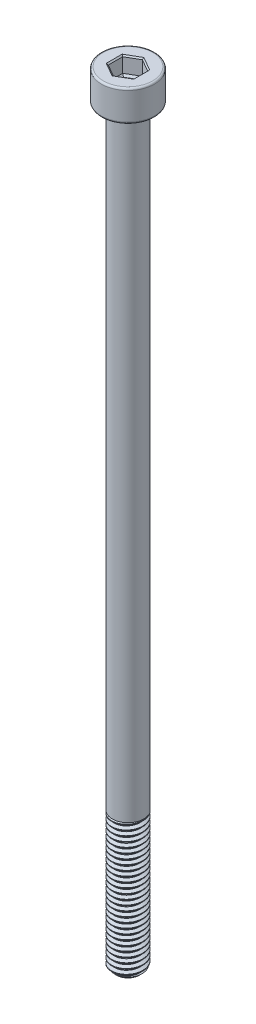
SolidWorks part; units mm, degrees
material "AISI Type A2 Tool Steel"
ref_plane "Front Plane" through (0, 0, 0) normal (0, 0, 1) x (1, 0, 0)
ref_plane "Top Plane" through (0, 0, 0) normal (0, 1, 0) x (1, 0, 0)
ref_plane "Right Plane" through (0, 0, 0) normal (1, 0, 0) x (0, 0, -1)
sketch "Sketch1" plane through (0, 0, 0) normal (0, 1, 0) x (1, 0, 0)
  circle A0 centre (0, 0) radius 2.5
  dimension "D1" = 5
extrude "Boss-Extrude1" add sketch "Sketch1" along normal blind 22
thread "Thread1" pitch 0.8 method cut profile "Thread Profile1" start angle 0, offset 1, length 0, pitch 0.8, diameter 5
ref_plane "Plane1" through (-2.5, 23, 0) normal (0, 0, 1) x (-1, 0, 0)
sketch "Thread Profile1" plane through (-2.5, 23, 0) normal (0, 0, 1) x (-1, 0, 0)
  line L0 (0, 0) -> (0, 0.8) construction
  line L11 (0, 0) -> (0, 0.7)
  line L12 (0, 0.7) -> (-0.433, 0.45)
  line L13 (-0.433, 0.45) -> (-0.433, 0.25)
  line L15 (-0.433, 0.25) -> (0, 0)
  line L17 (-0.433, 0.35) -> (0, 0.35) construction
  point P2 (0, 0)
  dimension "Pitch" = 0.8
  dimension "Profile_Angle" = 60
  dimension "Profile_Land" = 0.2
  dimension "Profile_Height" = 0.433
sketch "Sketch2" plane through (0, 22, 0) normal (0, 1, 0) x (1, 0, 0)
  circle A0 centre (0, 0) radius 2.5
  dimension "D1" = 5
extrude "Boss-Extrude2" add sketch "Sketch2" along normal blind 98
sketch "Sketch3" plane through (0, 120, 0) normal (0, 1, 0) x (1, 0, 0)
  circle A0 centre (0, 0) radius 4.25
  dimension "D1" = 8.5
extrude "Boss-Extrude3" add sketch "Sketch3" along normal blind 5
fillet "Fillet1" radius 0.3 2 edges at (0, 120, 4.25) (0, 125, 4.25)
sketch "Sketch4" plane through (0, 0, 0) normal (0, 0, 1) x (1, 0, 0)
  line L0 (0, 0) -> (0, 0.4416) construction
  line L1 (0, 0) -> (2.51, 0) construction
  line L2 (2.51, 0) -> (2.51, 0.7)
  line L3 (2.51, 0.7) -> (1.81, 0)
  line L4 (1.81, 0) -> (2.51, 0)
  dimension "D1" = 0.7
  dimension "D2" = 45
  dimension "D3" = 2.51
revolve "Cut-Revolve1" cut sketch "Sketch4" angle 360 about L0
sketch "Sketch5" plane through (0, 125, 0) normal (0, 1, 0) x (1, 0, 0)
  line L1 (0, 2.3094) -> (-2, 1.1547)
  line L2 (-2, 1.1547) -> (-2, -1.1547)
  line L3 (-2, -1.1547) -> (0, -2.3094)
  line L4 (0, -2.3094) -> (2, -1.1547)
  line L5 (2, -1.1547) -> (2, 1.1547)
  line L6 (2, 1.1547) -> (0, 2.3094)
  circle A0 centre (0, 0) radius 2 construction
  dimension "D1" = 4
extrude "Cut-Extrude1" cut sketch "Sketch5" against normal blind 2.5
chamfer "Chamfer1" distance 0.2 angle 45 6 edges at (-1, 125, 1.7321) (1, 125, 1.7321) (2, 125, 0) (1, 125, -1.7321) (-1, 125, -1.7321) (-2, 125, 0)
sketch "Sketch6" plane through (0, 122.5, 0) normal (0, 1, 0) x (1, 0, 0)
  line L1 (0, 2.3094) -> (-2, 1.1547)
  line L2 (-2, 1.1547) -> (-2, -1.1547)
  line L3 (-2, -1.1547) -> (0, -2.3094)
  line L4 (0, -2.3094) -> (2, -1.1547)
  line L5 (2, -1.1547) -> (2, 1.1547)
  line L6 (2, 1.1547) -> (0, 2.3094)
  circle A0 centre (0, 0) radius 2 construction
extrude "Cut-Extrude2" cut sketch "Sketch6" against normal blind 0.3 draft 45
